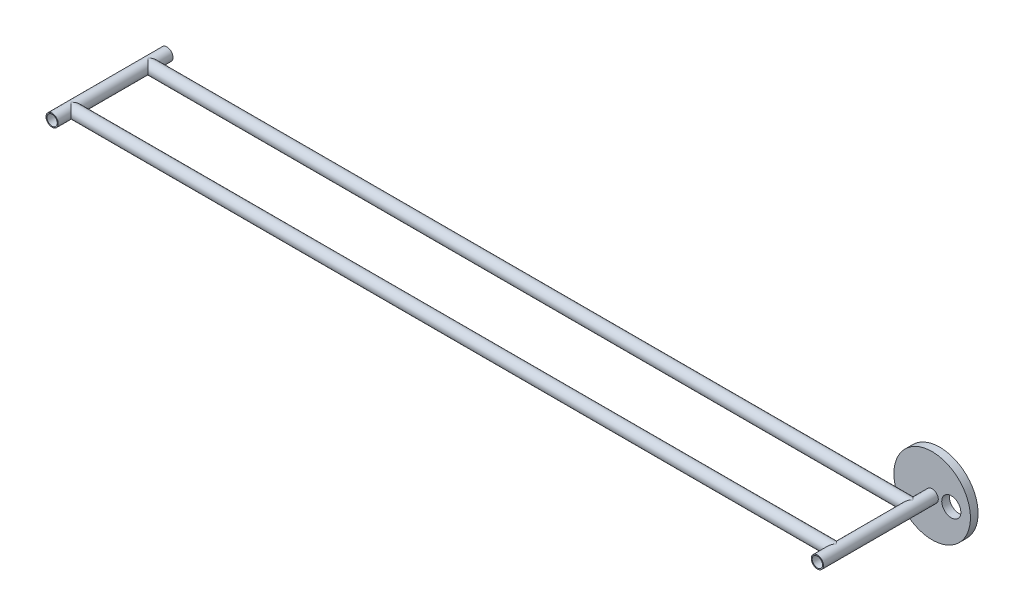
SolidWorks part; units mm, degrees
material "PVC Rigid"
ref_plane "Front Plane" through (0, 0, 0) normal (0, 0, 1) x (1, 0, 0)
ref_plane "Top Plane" through (0, 0, 0) normal (0, 1, 0) x (1, 0, 0)
ref_plane "Right Plane" through (0, 0, 0) normal (1, 0, 0) x (0, 0, -1)
sketch "Sketch1" plane through (0, 0, 0) normal (1, 0, 0) x (0, 0, -1)
  line L0 (-71.0406, 0) -> (82.5769, 0) construction
  circle A0 centre (-50, 0) radius 8
  circle A1 centre (-50, 0) radius 6.75
  circle A2 centre (50, 0) radius 6.75
  circle A3 centre (50, 0) radius 8
  dimension "D1" = 16
  dimension "D2" = 13.5
  dimension "D3" = 13.5
  dimension "D4" = 16
  dimension "D5" = 50
  dimension "D6" = 50
extrude "Boss-Extrude1" add sketch "Sketch1" along normal blind 1000
sketch "Sketch2" plane through (0, 0, 0) normal (0, 0, 1) x (1, 0, 0)
  circle A0 centre (0, 0) radius 8
  circle A1 centre (0, 0) radius 6.75
  dimension "D1" = 13.5
  dimension "D2" = 16
extrude "Boss-Extrude2" add sketch "Sketch2" along normal blind 75 and the other way blind 75
sketch "Sketch3" plane through (0, 0, 75) normal (0, 0, 1) x (1, 0, 0)
  circle A0 centre (0, 0) radius 6.75
  dimension "D1" = 13.5
extrude "Cut-Extrude1" cut sketch "Sketch3" against normal blind 150
sketch "Sketch4" plane through (0, 0, 0) normal (0, 0, 1) x (1, 0, 0)
  line L0 (1000, -8) -> (1000, 8) construction
  circle A0 centre (1000, 0) radius 8
  circle A1 centre (1000, 0) radius 6.75
  dimension "D1" = 16
  dimension "D2" = 13.5
extrude "Boss-Extrude3" add sketch "Sketch4" along normal blind 75 and the other way blind 75
sketch "Sketch6" plane through (0, 0, 75) normal (0, 0, 1) x (1, 0, 0)
  line L0 (1000, -6.75) -> (1000, 6.75) construction
  circle A0 centre (1000, 0) radius 6.75
  dimension "D1" = 13.5
extrude "Cut-Extrude2" cut sketch "Sketch6" against normal blind 150
sketch "Sketch7" plane through (0, 0, -75) normal (0, 0, -1) x (-1, 0, 0)
  line L0 (-1025, 0) -> (-1000, 0) construction
  circle A0 centre (-1000, 0) radius 50
  circle A1 centre (-1000, 0) radius 6.75
  circle A2 centre (-1025, 0) radius 12.5
  dimension "D1" = 100
  dimension "D2" = 13.5
  dimension "D3" = 25
  dimension "D4" = 25
extrude "Boss-Extrude4" add sketch "Sketch7" along normal blind 10
